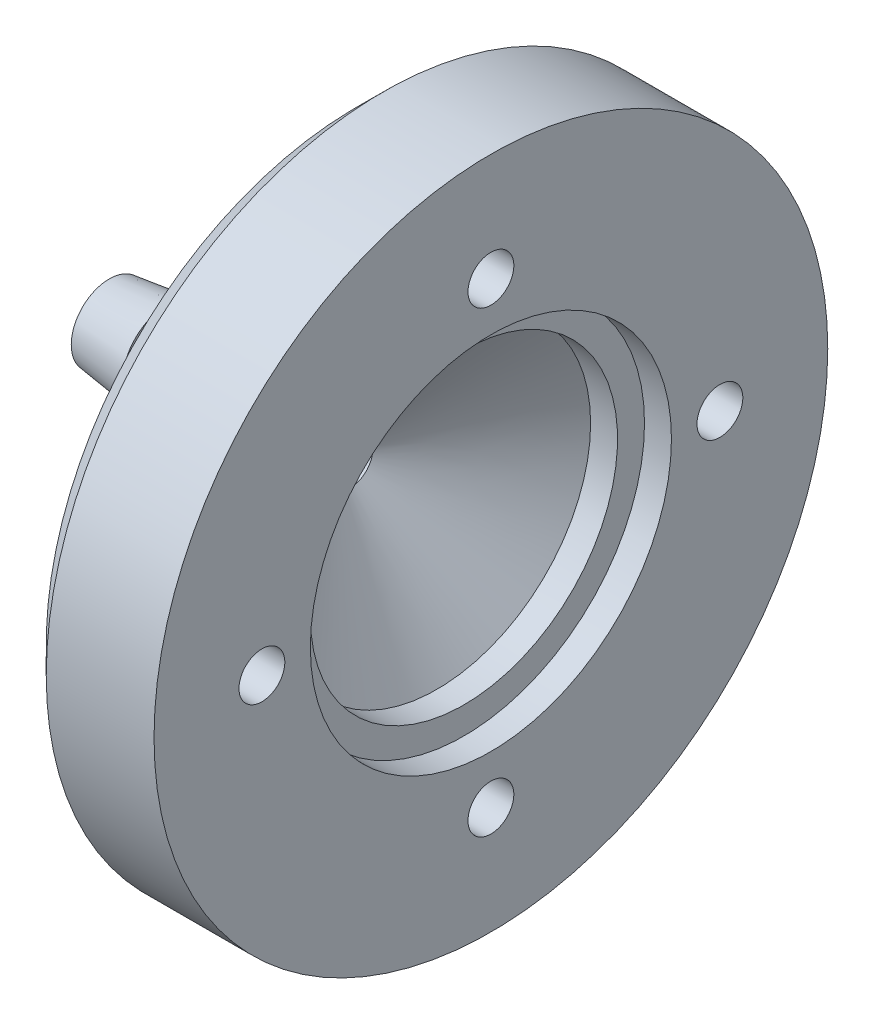
SolidWorks part; units mm, degrees
ref_plane "Front Plane" through (0, 0, 0) normal (0, 0, 1) x (1, 0, 0)
ref_plane "Top Plane" through (0, 0, 0) normal (0, 1, 0) x (1, 0, 0)
ref_plane "Right Plane" through (0, 0, 0) normal (1, 0, 0) x (0, 0, -1)
sketch "Sketch1" plane through (0, 0, 0) normal (0, 0, 1) x (1, 0, 0)
  line L0 (-801.9206, 0) -> (36107.5283, 0) construction
  line L3 (-13.5456, 3.375) -> (-13.5456, 2.82)
  line L8 (-17.879, 1.685) -> (0, 1.685)
  line L9 (-17.879, 1.685) -> (-17.879, 2.82)
  line L10 (10.4442, 13.4) -> (10.4442, 25)
  line L12 (10.4442, 25) -> (0.4442, 25)
  line L16 (10.4442, 13.4) -> (8.4442, 13.4)
  line L17 (8.4442, 13.4) -> (8.4442, 11.4)
  line L18 (0.4442, 25) -> (0.4442, 11.4)
  line L20 (0, 1.685) -> (6.4442, 11.4)
  line L21 (-17.879, 2.82) -> (-13.5456, 3.375)
  line L22 (6.4442, 11.4) -> (8.4442, 11.4)
  line L23 (-13.5456, 2.82) -> (-9.2123, 3.375)
  line L25 (-9.2123, 2.82) -> (-4.879, 3.375)
  line L26 (-9.2123, 3.375) -> (-9.2123, 2.82)
  line L27 (-4.879, 3.375) -> (0.4442, 11.4)
  point P3 (-61.7484, 13.8515)
  point P10 (-68.4593, 3.17)
  point P14 (0, 0)
  point P17 (-68.2799, 4.0431)
  point P20 (0, 0)
  point P21 (0, 0)
  point P22 (0, 0)
  point P23 (-68.1816, 3.17)
  point P24 (0, 0)
  point P25 (0, 0)
  point P27 (-61.0678, 25)
  point P28 (-63.828, 11.4)
  point P30 (-51.0715, 11.4)
  point P31 (-44.8475, 11.4)
  point P32 (-54.5076, 11.4)
  point P33 (0, 0)
  point P34 (0, 0)
  dimension "D3" = 2
  dimension "D2" = 6.75
  dimension "D6" = 3.37
  dimension "D7" = 5.64
  dimension "D1" = 10
  dimension "D5" = 25
  dimension "D8" = 13.4
  dimension "D10" = 2
  dimension "D4" = 5
  dimension "D9" = 2
  dimension "D11" = 13
revolve "Revolve17" add sketch "Sketch1" angle 360 about L0
sketch "Sketch4" plane through (0.4442, 0, 0) normal (-1, 0, 0) x (0, 0, 1)
  circle A0 centre (0, 0) radius 16.9947 construction
  point P3 (0, 16.9947)
  point P4 (0, 16.9947)
  point P7 (16.9947, 0)
  point P12 (-16.9947, 0)
  point P13 (0, -16.9947)
hole_wizard "CBORE for M3 Hex Socket Head Cap Screw2" positions "Sketch4" profile "Sketch5" counterbore size "M3" standard "ISO"
sketch "Sketch5" plane through (0.4442, -16.9947, 0) normal (0, 1, 0) x (0, 0, 1)
  line L0 (0, 0) -> (0, 11.0215)
  line L1 (0, 11.0215) -> (1.7, 10)
  line L2 (1.7, 10) -> (1.7, 3.4)
  line L3 (1.7, 3.4) -> (3.25, 3.4)
  line L4 (3.25, 3.4) -> (3.25, 0)
  line L5 (3.25, 0) -> (0, 0)
  line L10 (0, 11.0215) -> (-1.7, 10) construction
  line L11 (0, -6.35) -> (0, 107.95) construction
  dimension "Hole Dia." = 3.4
  dimension "Hole Depth" = 10
  dimension "C'Bore Dia." = 6.5
  dimension "C'Bore Depth" = 3.4
  dimension "Drill Angle" = 118
chamfer "Chamfer1" distance 2 angle 45 1 edges at (0.4442, 0, 25)
equation "\"D10@Sketch1\"=\"D3@Sketch1\""
equation "\"D9@Sketch1\"=\"D3@Sketch1\""
